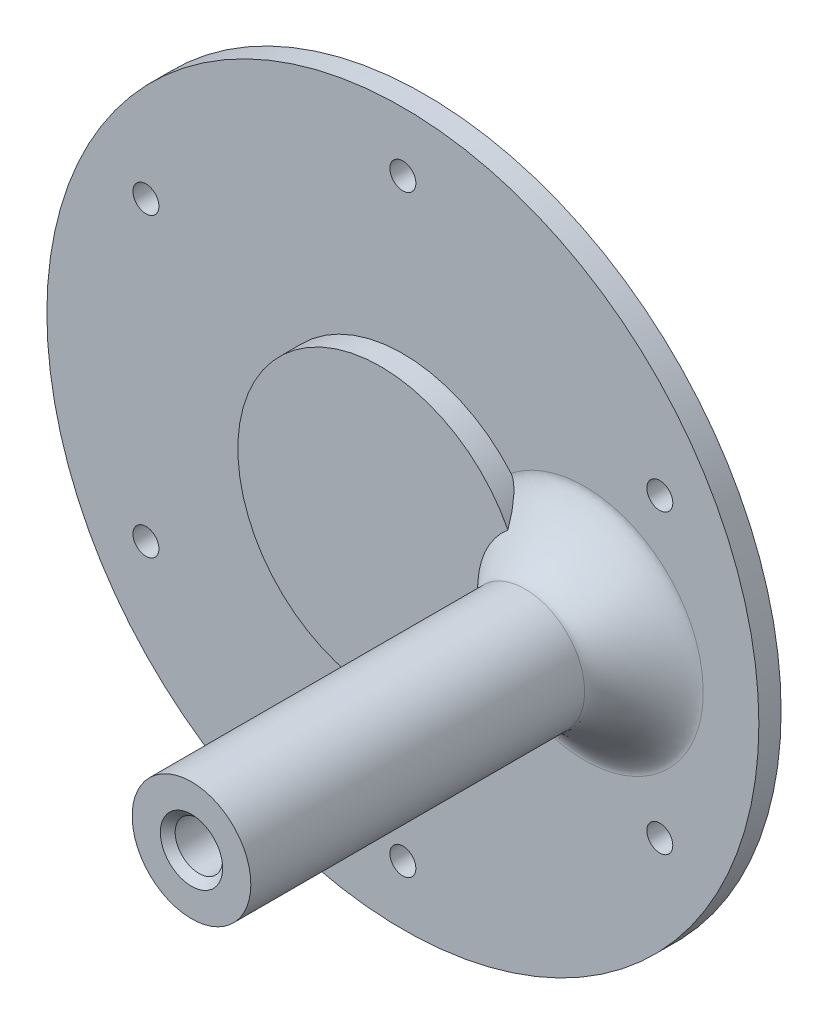
SolidWorks part; units mm, degrees
ref_plane "Front Plane" through (0, 0, 0) normal (0, 0, 1) x (1, 0, 0)
ref_plane "Top Plane" through (0, 0, 0) normal (0, 1, 0) x (1, 0, 0)
ref_plane "Right Plane" through (0, 0, 0) normal (1, 0, 0) x (0, 0, -1)
sketch "Sketch1" plane through (0, 0, 0) normal (0, 0, 1) x (1, 0, 0)
  circle A0 centre (0, 0) radius 48
extrude "Boss-Extrude1" add sketch "Sketch1" along normal blind 3
sketch "Sketch2" plane through (0, 0, 3) normal (0, 0, 1) x (1, 0, 0)
  circle A0 centre (0, 40) radius 1.75
extrude "Cut-Extrude1" cut sketch "Sketch2" against normal blind 3
pattern_circular "CirPattern1" count 6 over 360 of "Cut-Extrude1"
sketch "Sketch3" plane through (0, 0, 3) normal (0, 0, 1) x (1, 0, 0)
  circle A0 centre (24.5, 0) radius 8
  dimension "D1" = 16
extrude "Boss-Extrude2" add sketch "Sketch3" along normal blind 53
sketch "Sketch4" plane through (0, 0, 56) normal (0, 0, 1) x (1, 0, 0)
  circle A0 centre (24.5, 0) radius 3.2
  dimension "D1" = 6.4
extrude "Cut-Extrude2" cut sketch "Sketch4" against normal through all
chamfer "Chamfer1" distance 1 angle 45 1 edges at (27.7, 0, 56)
fillet "Fillet1" radius 8 1 edges at (32.5, 0, 3) conic rho 0.2
sketch "Sketch5" plane through (0, 0, 3) normal (0, 0, 1) x (1, 0, 0)
  circle A0 centre (0, 0) radius 19.25
extrude "Boss-Extrude3" add sketch "Sketch5" along normal blind 3
